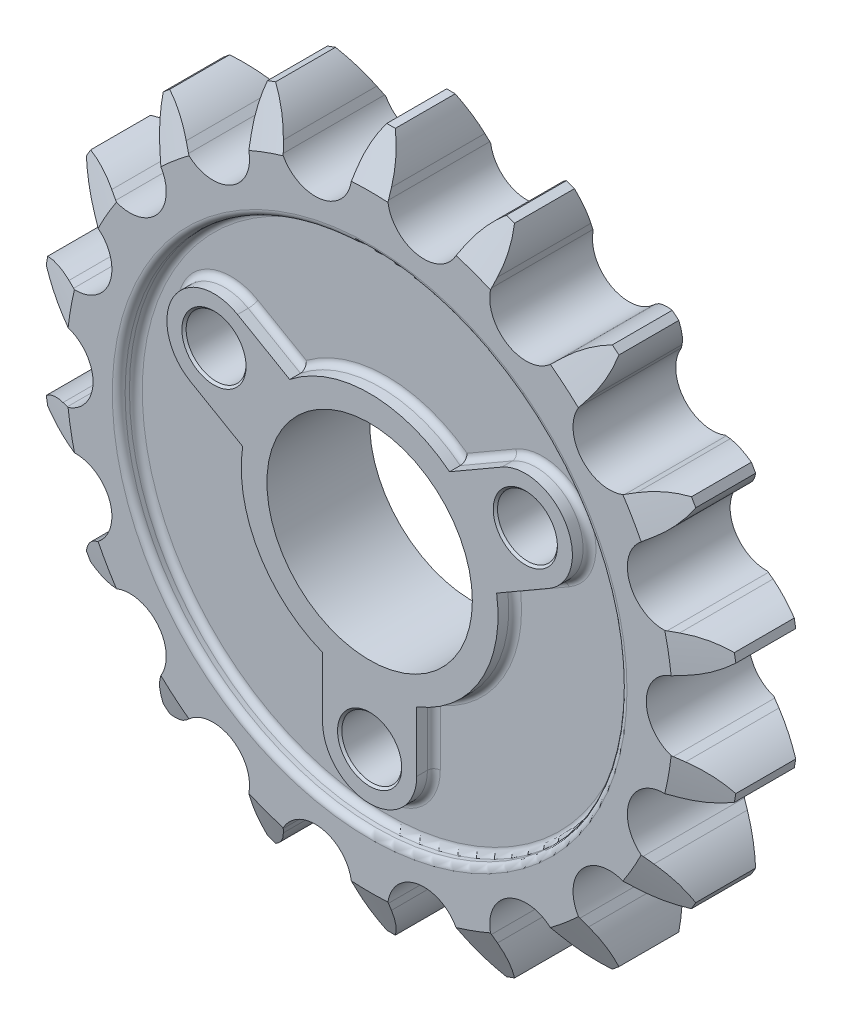
SolidWorks part; units mm, degrees
ref_plane "Front Plane" through (0, 0, 0) normal (0, 0, 1) x (1, 0, 0)
ref_plane "Top Plane" through (0, 0, 0) normal (0, 1, 0) x (1, 0, 0)
ref_plane "Right Plane" through (0, 0, 0) normal (1, 0, 0) x (0, 0, -1)
sketch "Sketch1" plane through (0, 0, 0) normal (0, 0, 1) x (1, 0, 0)
  line L0 (0, 0) -> (0, 36.5682) construction
  line L1 (-2.1183, 35.5682) -> (2.1183, 35.5682) construction
  line L2 (-2.1183, 35.5682) -> (-2.0043, 36.5682) construction
  line L3 (2.1183, 35.5682) -> (2.0043, 36.5682) construction
  line L4 (-2.0043, 36.5682) -> (2.0043, 36.5682) construction
  line L7 (-0.5, 40.8131) -> (0.5, 40.8131) construction
  circle A0 centre (0, 0) radius 36.5682 construction
  circle A1 centre (6.35, 36.0126) radius 4.255 construction
  circle A2 centre (-6.35, 36.0126) radius 4.255 construction
  circle A3 centre (0, 0) radius 32.3132 construction
  arc A4 (-2.0043, 36.5682) -> (-0.5, 40.8131) centre (7.9314, 35.4362) cw construction
  arc A5 (2.0043, 36.5682) -> (0.5, 40.8131) centre (-7.9314, 35.4362) ccw construction
  dimension "D1" = 13
  dimension "SprocketPitchDiameter" = 73.1364
  dimension "RollerDia" = 8.51
  dimension "D4" = 10
  dimension "ChainPitch" = 12.7
  dimension "D2" = 1
  dimension "D3" = 1
  dimension "D5" = 1
sketch "Sketch8" plane through (0, 0, 0) normal (0, 0, 1) x (1, 0, 0)
  line L0 (0, 0) -> (-18.1865, 10.5) construction
  line L2 (0, 0) -> (0, -45.2986) construction
  line L4 (-15.4365, 15.2631) -> (-9.3356, 11.7408)
  line L5 (-20.9365, 5.7369) -> (-14.8356, 2.2145)
  arc A2 (-14.8356, 2.2145) -> (-9.3356, 11.7408) centre (0, 0) ccw
  circle A9 centre (-18.1865, 10.5) radius 3.5 construction
  arc A12 (-15.4365, 15.2631) -> (-20.9365, 5.7369) centre (-18.1865, 10.5) ccw
  dimension "D1" = 120
  dimension "D2" = 21
  dimension "D4" = 15
  dimension "D3" = 7
  dimension "D7" = 5.5
sketch "Sketch2" plane through (0, 0, 0) normal (0, 0, 1) x (1, 0, 0)
  circle A0 centre (0, 0) radius 32.3132 construction
  circle A1 centre (0, 0) radius 32.3132
extrude "Boss-Extrude1" add sketch "Sketch2" along normal mid plane 12
sketch "Sketch4" plane through (0, 0, 0) normal (0, 0, 1) x (1, 0, 0)
  line L0 (-0.5, 40.8131) -> (0.5, 40.8131) construction
  line L1 (-2.1183, 35.5682) -> (-2.0043, 36.5682) construction
  line L2 (2.1183, 35.5682) -> (2.0043, 36.5682) construction
  line L3 (-0.5, 40.8131) -> (0.5, 40.8131)
  line L4 (-2.1183, 35.5682) -> (-2.0043, 36.5682)
  line L5 (2.1183, 35.5682) -> (2.0043, 36.5682)
  circle A0 centre (0, 0) radius 32.3132 construction
  circle A1 centre (6.35, 36.0126) radius 4.255 construction
  circle A2 centre (-6.35, 36.0126) radius 4.255 construction
  arc A3 (2.0043, 36.5682) -> (0.5, 40.8131) centre (-7.9314, 35.4362) ccw construction
  arc A4 (-0.5, 40.8131) -> (-2.0043, 36.5682) centre (7.9314, 35.4362) ccw construction
  arc A5 (5.6111, 31.8223) -> (-5.6111, 31.8223) centre (0, 0) ccw
  arc A6 (2.1183, 35.5682) -> (5.6111, 31.8223) centre (6.35, 36.0126) ccw
  arc A7 (-5.6111, 31.8223) -> (-2.1183, 35.5682) centre (-6.35, 36.0126) ccw
  arc A8 (2.0043, 36.5682) -> (0.5, 40.8131) centre (-7.9314, 35.4362) ccw
  arc A9 (-0.5, 40.8131) -> (-2.0043, 36.5682) centre (7.9314, 35.4362) ccw
extrude "Boss-Extrude2" add sketch "Sketch4" along normal up to surface and the other way up to surface up to face at (32.3132, 0, 6) other way up to face at (32.3132, 0, -6)
pattern_circular "CirPattern1" count 18 over 360 about axis through (0, 0, 6) along (0, 0, -1) of "Boss-Extrude2"
sketch "Sketch5" plane through (0, 0, 0) normal (1, 0, 0) x (0, 0, -1)
  line L0 (0, 0) -> (-7, 0) construction
  line L1 (0, 40.8131) -> (0, 36.5682) construction
  line L2 (-7, 48.3131) -> (7, 48.3131)
  line L3 (-7, 48.3131) -> (-7, 33.3131)
  line L4 (-7, 33.3131) -> (7, 33.3131) construction
  line L5 (7, 48.3131) -> (7, 33.3131)
  line L6 (-7, 48.3131) -> (7, 33.3131) construction
  line L7 (-7, 33.3131) -> (7, 48.3131) construction
  line L8 (-7, 33.3131) -> (0, 48.3131)
  line L9 (7, 33.3131) -> (0, 48.3131)
  line L10 (0, 40.8131) -> (0, 36.5682) construction
  point P1 (0, 40.8131)
  dimension "D1" = 15
  dimension "D2" = 1
revolve "Cut-Revolve7" cut sketch "Sketch5" angle 360 about L0 region at (0, 43.3131, -4.6667) region at (0, 43.3131, 4.6667)
sketch "Sketch9" plane through (0, 0, 0) normal (0, 0, 1) x (1, 0, 0)
  circle A0 centre (0, 0) radius 29.3132
  circle A1 centre (0, 0) radius 32.3132 construction
  dimension "D1" = 3
extrude "Cut-Extrude2" cut sketch "Sketch9" against normal blind 2 from surface contours A0 starting at face at (0, 0, 6)
sketch "Sketch7" plane through (0, 0, 0) normal (0, 0, 1) x (1, 0, 0)
  circle A0 centre (0, 0) radius 12
  dimension "D1" = 24
extrude "Boss-Extrude3" add sketch "Sketch8" along normal up to surface (6 mm away) contours L5 A2 L4 A12 up to face at (29.3132, 0, 6)
sketch "Sketch11" plane through (0, 0, 0) normal (0, 0, 1) x (1, 0, 0)
  circle A0 centre (-18.1865, 10.5) radius 3.5 construction
  circle A1 centre (-18.1865, 10.5) radius 3.5
extrude "Cut-Extrude4" cut sketch "Sketch11" against normal through all both and the other way through all
pattern_circular "CirPattern3" count 3 over 360 about axis through (0, 0, 6) along (0, 0, 1) of "Boss-Extrude3", "Cut-Extrude4"
extrude "Cut-Extrude3" cut sketch "Sketch7" against normal through all both and the other way through all contours A0
fillet "Fillet1" radius 0.75 14 edges at (29.3132, 0, 4) (29.3132, 0, 6) (-17.8861, 3.9757, 4) (-12.3861, 13.502, 4) (-22.9497, 13.25, 4) (0, -26.5, 4) (5.5, -17.4776, 4) (12.9904, -7.5, 4) (17.8861, 3.9757, 4) (22.9497, 13.25, 4) (12.3861, 13.502, 4) (0, 15, 4) (-12.9904, -7.5, 4) (-5.5, -17.4776, 4)
chamfer "Chamfer1" distance 0.25 angle 45 6 edges at (-1.75, -17.9689, 6) (-1.75, -17.9689, -6) (16.4365, 7.4689, 6) (16.4365, 7.4689, -6) (-14.6865, 10.5, 6) (-14.6865, 10.5, -6)
equation "\"ChainPitch\"=12.7"
equation "\"ChainPitch@Sketch1\"=\"ChainPitch\""
equation "\"SprocketPitchDiameter@Sketch1\" = \"ChainPitch\" / sin ( 180 / \"NumberOfTeeth\" )"
equation "\"NumberOfTeeth\"= 18"
equation "\"D1@CirPattern1\"=\"NumberOfTeeth\""
